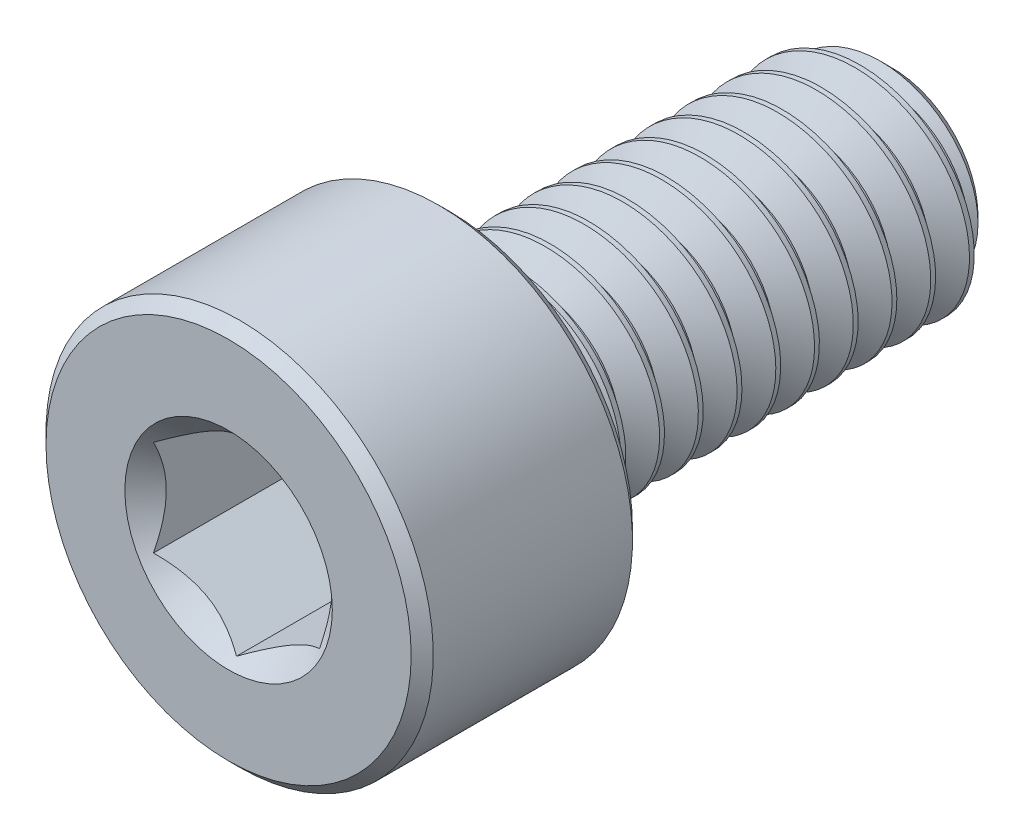
SolidWorks part; units mm, degrees
ref_plane "Front Plane" through (0, 0, 0) normal (0, 0, 1) x (1, 0, 0)
ref_plane "Top Plane" through (0, 0, 0) normal (0, 1, 0) x (1, 0, 0)
ref_plane "Right Plane" through (0, 0, 0) normal (1, 0, 0) x (0, 0, -1)
sketch "Sketch1" plane through (0, 0, 0) normal (1, 0, 0) x (0, 0, -1)
  line L0 (-6, 0) -> (6, 0) construction
  line L1 (6, 0) -> (6, 1.5453) construction
  line L2 (6, 1.5453) -> (5.5453, 2) construction
  line L3 (5.5453, 2) -> (5.475, 2) construction
  line L4 (5.475, 2) -> (-2, 2) construction
  line L5 (-2, 2) -> (-2, 3.5) construction
  line L6 (-2, 3.5) -> (-6, 3.5) construction
  line L7 (-6, 3.5) -> (-6, 0) construction
  line L8 (6, 1.5453) -> (6, 2) construction
  line L9 (5.9562, 2.0758) -> (6.3062, 1.4696) construction
  line L10 (6.3062, 1.4696) -> (6.6562, 2.0758) construction
  line L11 (6.6562, 2.0758) -> (5.9562, 2.0758) construction
  line L12 (6.3062, 2.0758) -> (6.3062, 2) construction
  line L13 (6.3062, 1.4696) -> (6.3062, 1.5453) construction
  line L14 (6.2625, 1.5453) -> (6.35, 1.5453) construction
  line L15 (6, 2) -> (6.6125, 2) construction
  line L16 (5.9781, 2.0379) -> (6.6344, 2.0379) construction
  line L17 (6, 0) -> (6, -2) construction
  line L18 (-2.2, 3.5) -> (-2, 3.3) construction
  line L19 (-5.8, 3.5) -> (-6, 3.3) construction
  line L20 (-2, 2) -> (-2, 0) construction
  line L21 (-2, 1) -> (0.6667, 1) construction
  line L22 (0.6667, 1) -> (3.3333, 1) construction
  line L23 (3.3333, 1) -> (6, 1) construction
  line L24 (0.6667, 1) -> (0.6667, 2) construction
  line L25 (0.6667, 2) -> (0.6667, 3.5) construction
  line L26 (3.3333, 1) -> (3.3333, 3.5) construction
  point P0 (-6, 1.5)
  point P3 (4.25, 2)
  point P4 (0, 0)
  point P18 (3.3333, 2)
  point P22 (6.3062, 1.5453)
  point P24 (5.475, 2)
  point P25 (6.3062, 2)
  point P28 (6.3062, 2.0379)
  point P29 (4.25, -2)
  point P30 (0.6667, 2)
  point P31 (-4, 3.5)
  point P37 (-2.7, 3.5)
  point P38 (-5.7, 3.5)
  point P45 (0.6667, 1)
  point P46 (3.3333, 1)
  dimension "D2" = 0.0875
  dimension "D7" = 0.2
  dimension "D8" = 0.2
  dimension "D9" = 0.2
  dimension "D10" = 0.1
  dimension "D11" = 0.5
  dimension "Drive Size" = 3
  dimension "Head Diameter" = 7
  dimension "Head Height" = 4
  dimension "Thread Pitch" = 0.7
  dimension "Thread Size" = 4
  dimension "Length" = 8
  dimension "D12" = 0.525
  dimension "D4" = 1.75
  dimension "D3" = 45
sketch "Sketch2" plane through (0, 0, 0) normal (1, 0, 0) x (0, 0, -1)
  line L0 (-6, 0) -> (-6, 3.3)
  line L1 (-5.8, 3.5) -> (-2.2, 3.5)
  line L2 (-2, 3.3) -> (-2, 2.2)
  line L4 (5.5453, 2) -> (6, 1.5453)
  line L5 (6, 1.5453) -> (6, 0)
  line L6 (-2, 3.5) -> (-6, 3.5) construction
  line L7 (6, 0) -> (-6, 0)
  line L8 (-5.8, 3.5) -> (-6, 3.3) construction
  line L10 (-5.8, 3.5) -> (-6, 3.3)
  line L14 (-2.2, 3.5) -> (-2, 3.3) construction
  line L16 (-2.2, 3.5) -> (-2, 3.3)
  line L17 (-2, 2) -> (-2, 3.5) construction
  line L19 (-1.8, 2) -> (5.5453, 2)
  line L20 (5.475, 2) -> (-2, 2) construction
  arc A1 (-2, 2.2) -> (-1.8, 2) centre (-1.8, 2.2) ccw
  dimension "D3" = 0.2
revolve "Revolve1" add sketch "Sketch2" angle 360 about L7
sketch "Sketch3" plane through (0, 0, 6) normal (0, 0, 1) x (1, 0, 0)
  line L1 (1.5, -0.866) -> (1.5, 0.866)
  line L2 (1.5, 0.866) -> (0, 1.7321)
  line L3 (0, 1.7321) -> (-1.5, 0.866)
  line L4 (-1.5, 0.866) -> (-1.5, -0.866)
  line L5 (-1.5, -0.866) -> (0, -1.7321)
  line L6 (0, -1.7321) -> (1.5, -0.866)
  circle A0 centre (0, 0) radius 1.5 construction
  circle A1 centre (0, 0) radius 3.5 construction
  circle A2 centre (0, 0) radius 3.5 construction
  circle A3 centre (0, 0) radius 1.7321 construction
  point P13 (0, 0)
extrude "Cut-Extrude1" cut sketch "Sketch3" against normal offset from surface (3 mm away) 1 up to face at (0, 3.3, 2)
sketch "Sketch4" plane through (0, 0, 6) normal (0, 0, 1) x (1, 0, 0)
  circle A0 centre (0, 0) radius 1.875
  dimension "D1" = 3.75
extrude "Cut-Extrude2" cut sketch "Sketch4" against normal up to vertex (2 mm away) draft 45 up to point (0, 3.5, 4)
sketch "Sketch11" plane through (0, 0, 0) normal (1, 0, 0) x (0, 0, -1)
  line L0 (-6, 0) -> (6, 0) construction
  line L1 (-6, 0) -> (6, 0) construction
  line L2 (-0.5, 0) -> (-0.5, 2) construction
  line L3 (5.475, 2) -> (-2, 2) construction
  line L4 (4.5, 0) -> (4.5, 2) construction
  line L6 (6, 1.5453) -> (6, 2) construction
  point P2 (-0.5, 0)
  point P3 (4.5, 0)
  dimension "D1" = 1.5
  dimension "D2" = 1.5
sketch "Sketch6" plane through (0, 0, -6) normal (0, 0, -1) x (-1, 0, 0)
  circle A0 centre (0, 0) radius 2
curve "Helix/Spiral1" pitch 0.7 height 8.7 radius 2 centre (0, 0, -6) axis (0, 0, 1) start towards (0, 1, 0)
sketch "Sketch10" plane through (0, 0, 0) normal (1, 0, 0) x (0, 0, -1)
  line L0 (-1.8, -3.5) -> (-1.8, 3.5)
  line L5 (-6, 0) -> (6, 0) construction
  line L6 (-1.8, 2) -> (-1.8, -2) construction
  point P3 (-1.8, 0)
split "Split1" trim tools "Sketch10" bodies to split 106 resulting bodies 114 115
sketch "Sketch7" plane through (0, 0, 0) normal (1, 0, 0) x (0, 0, -1)
  line L0 (5.9781, 2.0379) -> (6.6344, 2.0379)
  line L1 (6.6344, 2.0379) -> (6.35, 1.5453)
  line L2 (6.35, 1.5453) -> (6.2625, 1.5453)
  line L3 (6.2625, 1.5453) -> (5.9781, 2.0379)
sweep "Cut-Sweep1" cut profiles "Sketch7" path "Helix/Spiral1" align with end faces yes
sketch "Sketch8" plane through (0, 0, 0) normal (1, 0, 0) x (0, 0, -1)
  line L0 (-2, 0) -> (-2, 2)
  line L1 (-1.8, -2) -> (-1.8, 2) construction
  line L2 (-2, 2) -> (-1.8, 2)
  line L4 (-1.8, 2) -> (-0.6453, 0)
  line L5 (-0.6453, 0) -> (-2, 0)
  line L6 (5.475, 2) -> (-2, 2) construction
  line L7 (-6, 0) -> (6, 0) construction
  dimension "D1" = 60
revolve "Revolve2" add sketch "Sketch8" angle 360 about L5
equation "\"D2@Sketch1\" = \"Thread Pitch@Sketch1\" / 8"
equation "\"D4@Helix/Spiral1\" = \"Thread Pitch@Sketch1\""
equation "\"D7@Sketch1\" = \"Head Height@Sketch1\" * .05"
equation "\"D8@Sketch1\"=\"D7@Sketch1\""
equation "\"D9@Sketch1\"=\"D7@Sketch1\""
equation "\"D10@Sketch1\"=\"D7@Sketch1\"/2"
equation "\"D11@Sketch1\"=\"D10@Sketch1\"*5"
equation "\"D4@Sketch1\"=\"Thread Pitch@Sketch1\"*2.5"
equation "\"D12@Sketch1\"=\"Thread Pitch@Sketch1\"*.75"
equation "\"D3@Helix/Spiral1\"=\"Length@Sketch1\"+\"Thread Pitch@Sketch1\""
equation "\"D3@Sketch2\" = \"Thread Size@Sketch1\" * 0.05"
equation "\"D1@Sketch11\"=\"Length@Sketch1\"*0.1875"
equation "\"D2@Sketch11\"=\"D1@Sketch11\""
equation "\"D1@Sketch4\"=\"Drive Size@Sketch1\"*1.25"
